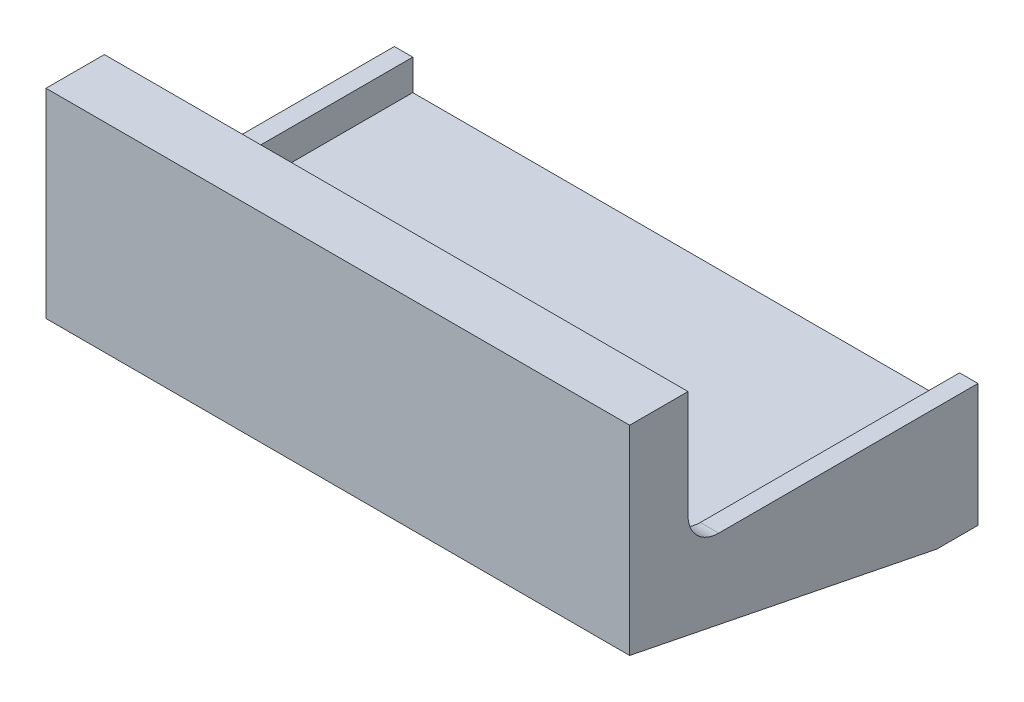
SolidWorks part; units mm, degrees
material "PLA"
ref_plane "Front Plane" through (0, 0, 0) normal (0, 0, 1) x (1, 0, 0)
ref_plane "Top Plane" through (0, 0, 0) normal (0, 1, 0) x (1, 0, 0)
ref_plane "Right Plane" through (0, 0, 0) normal (1, 0, 0) x (0, 0, -1)
sketch "Sketch1" plane through (0, 0, 0) normal (0, 0, 1) x (1, 0, 0)
  line L0 (-149, 38.5) -> (-149, 15.5) construction
  line L1 (-149, 38.5) -> (-149, 15.5) construction
  line L2 (-61, 15.5) -> (-61, 38.5) construction
  line L3 (-61, 15.5) -> (-61, 38.5) construction
  line L4 (-62, 15.5) -> (-148, 15.5) construction
  line L5 (-61, 15.5) -> (-149, 15.5) construction
  line L6 (-60.5, 15) -> (-60.5, 20)
  line L7 (-60.5, 15) -> (-149.5, 15)
  line L8 (-149.5, 20) -> (-149.5, 15)
  line L9 (-60.5, 15) -> (-60.5, 38.5) construction
  line L10 (-60.5, 20) -> (-57.5, 20)
  line L11 (-57.5, 20) -> (-57.5, 0)
  line L12 (-57.5, 0) -> (-152.5, 0)
  line L13 (-152.5, 0) -> (-152.5, 20)
  line L14 (-149.5, 38.5) -> (-149.5, 15) construction
  line L15 (-152.5, 20) -> (-149.5, 20)
  line L16 (0, 0) -> (-320, 0) construction
  dimension "D2" = 95
  dimension "D3" = 20
  dimension "D1" = 0.5
extrude "Boss-Extrude1" add sketch "Sketch1" along normal offset from surface (53.2 mm away) 0.5 offset beyond the face yes
sketch "Sketch2" plane through (0, 0, 53.2) normal (0, 0, 1) x (1, 0, 0)
  line L1 (-152.5, 20) -> (-57.5, 20)
  line L2 (-152.5, 20) -> (-152.5, 0)
  line L3 (-152.5, 0) -> (-57.5, 0)
  line L4 (-57.5, 20) -> (-57.5, 0)
extrude "Boss-Extrude2" add sketch "Sketch2" along normal blind 3.5
chamfer "Chamfer1" distance 50 distance2 10 1 edges at (-105, 0, 56.7) first distance on face at (-105, 0, 28.35)
sketch "Sketch3" plane through (0, 0, 56.7) normal (0, 0, 1) x (1, 0, 0)
  line L0 (-152.5, 20) -> (-57.5, 20)
  line L1 (-152.5, 20) -> (-152.5, 42.4638)
  line L2 (-57.5, 20) -> (-57.5, 42.4638)
  line L3 (-152.5, 42.4638) -> (-57.5, 42.4638)
  line L4 (-149, 15.5) -> (-149, 38.5) construction
  line L7 (-149, 20) -> (-149, 38.5) construction
  line L8 (-148, 38.5) -> (-62, 38.5) construction
  line L9 (-149, 38.5) -> (-61, 38.5) construction
  line L10 (-61, 38.5) -> (-61, 15.5) construction
  line L11 (-61, 38.5) -> (-61, 20) construction
  line L12 (-57.5, 20) -> (-152.5, 20) construction
  line L13 (-149.5, 20) -> (-149.5, 39)
  line L14 (-149.5, 39) -> (-60.5, 39)
  line L15 (-60.5, 39) -> (-60.5, 20)
  line M11 (-57.5, 20) -> (-152.5, 20)
  dimension "D1" = 0.5
extrude "Boss-Extrude3" add sketch "Sketch3" against normal up to surface (3.5 mm away) contours L15 L14 L13 L0 | L14 L15 L2 L3 L1 L0 L13 M11 region at (-151.5238, 31.2319, 56.7) region at (-105, 29.5, 56.7) up to face at (-105, 17.5, 53.2)
extrude "Boss-Extrude4" add sketch "Sketch3<3>" against normal blind 6 from surface contours L14 L15 L2 L3 L1 L0 L13 M11 region at (-151.5238, 31.2319, 56.7) starting at face at (-105, 24.366, 53.2)
sketch "Sketch3<3>" plane through (0, 0, 56.7) normal (0, 0, 1) x (1, 0, 0) same geometry as "Sketch3"
fillet "Fillet1" radius 5 2 edges at (-151, 20, 47.2) (-59, 20, 47.2)
sketch "Sketch4" plane through (0, 0, 0) normal (0, 0, -1) x (-1, 0, 0)
  point P0 (70, 5.6)
  point P1 (140, 5.6)
hole_wizard "Ø2.5mm Dowel Hole1" positions "Sketch4" profile "Sketch5" hole size "Ø2.5" standard "ANSI Metric"
sketch "Sketch5" plane through (-70, 5.6, 0) normal (1, 0, 0) x (0, 1, 0)
  line L0 (0, 0) -> (0, 7.4614)
  line L1 (0, 7.4614) -> (1.6, 6.5)
  line L2 (1.6, 6.5) -> (1.6, 0)
  line L5 (1.6, 0) -> (0, 0)
  line L10 (0, 7.4614) -> (-1.6, 6.5) construction
  line L11 (0, -6.35) -> (0, 107.95) construction
  dimension "Hole Dia." = 3.2
  dimension "Hole Depth" = 6.5
  dimension "Drill Angle" = 118
chamfer "Chamfer2" distance 0.5 angle 45 2 edges at (-141.6, 5.6, 0) (-71.6, 5.6, 0)
